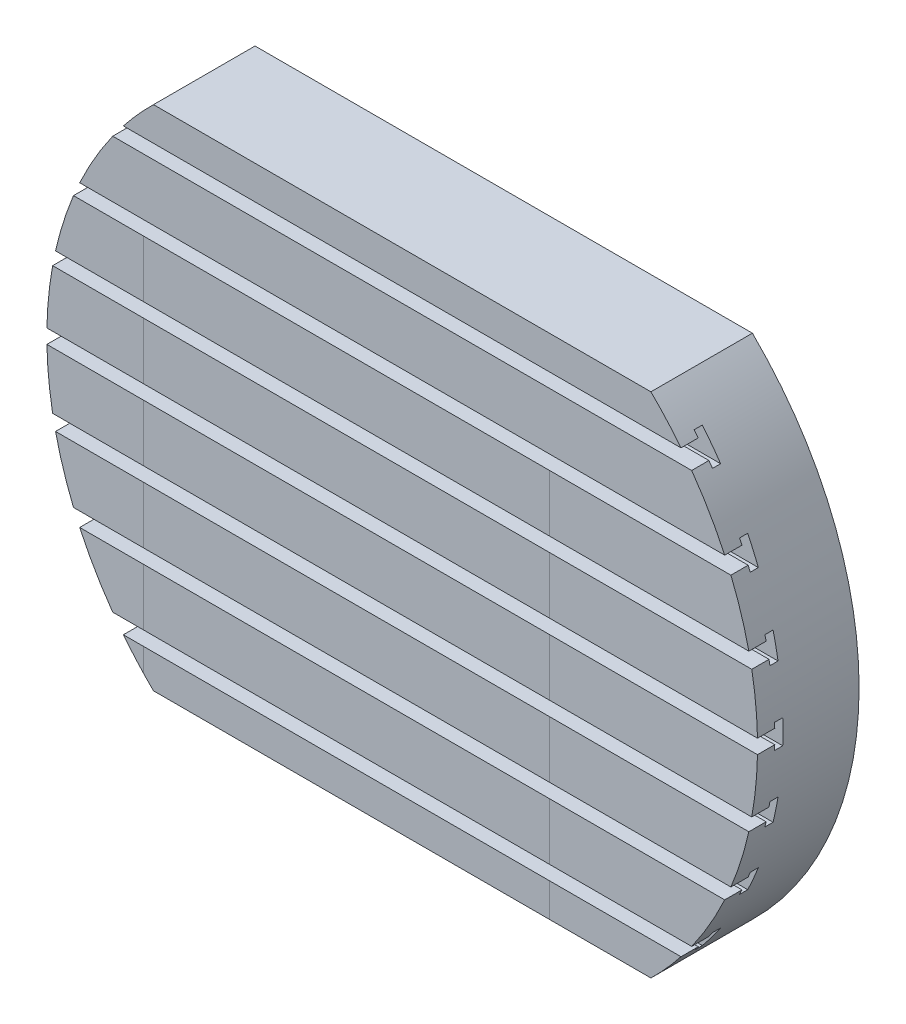
SolidWorks part; units mm, degrees
material "Plain Carbon Steel"
ref_plane "Front Plane" through (0, 0, 0) normal (0, 0, 1) x (1, 0, 0)
ref_plane "Top Plane" through (0, 0, 0) normal (0, 1, 0) x (1, 0, 0)
ref_plane "Right Plane" through (0, 0, 0) normal (1, 0, 0) x (0, 0, -1)
sketch "Sketch1" plane through (0, 0, 0) normal (0, 0, 1) x (1, 0, 0)
  circle A0 centre (0, 0) radius 350
  dimension "D1" = 700
extrude "Boss-Extrude1" add sketch "Sketch1" along normal blind 100
sketch "Sketch2" plane through (0, 0, 0) normal (1, 0, 0) x (0, 0, -1)
  line L0 (-100, 7) -> (-83, 7)
  line L1 (-100, 350) -> (-100, -350) construction
  line L2 (-83, 7) -> (-83, 12)
  line L3 (-83, 12) -> (-75, 12)
  line L4 (-75, 12) -> (-75, -12)
  line L5 (-75, -12) -> (-83, -12)
  line L6 (-83, -12) -> (-83, -7)
  line L7 (-83, -7) -> (-100, -7)
  line L8 (-100, -7) -> (-100, 7)
  line L9 (-100, 0) -> (-75, 0) construction
  line L10 (-83, 7) -> (-83, -7) construction
  line L11 (-100, -77) -> (-100, -63)
  line L12 (-100, -63) -> (-83, -63)
  line L13 (-83, -77) -> (-100, -77)
  line L14 (-83, -82) -> (-83, -77)
  line L15 (-75, -82) -> (-83, -82)
  line L16 (-75, -58) -> (-75, -82)
  line L17 (-83, -58) -> (-75, -58)
  line L18 (-83, -63) -> (-83, -58)
  line L19 (-100, -147) -> (-100, -133)
  line L20 (-100, -133) -> (-83, -133)
  line L21 (-83, -147) -> (-100, -147)
  line L22 (-83, -152) -> (-83, -147)
  line L23 (-75, -152) -> (-83, -152)
  line L24 (-75, -128) -> (-75, -152)
  line L25 (-83, -128) -> (-75, -128)
  line L26 (-83, -133) -> (-83, -128)
  line L27 (-100, -217) -> (-100, -203)
  line L28 (-100, -203) -> (-83, -203)
  line L29 (-83, -217) -> (-100, -217)
  line L30 (-83, -222) -> (-83, -217)
  line L31 (-75, -222) -> (-83, -222)
  line L32 (-75, -198) -> (-75, -222)
  line L33 (-83, -198) -> (-75, -198)
  line L34 (-83, -203) -> (-83, -198)
  line L43 (0, -350) -> (0, 350) construction
  line L44 (-100, -350) -> (0, -350)
  line L45 (-100, -350) -> (-100, -250)
  line L46 (-100, -250) -> (0, -250)
  line L47 (0, -350) -> (0, -250)
  line L48 (-100, 63) -> (-100, 77)
  line L49 (-100, 350) -> (0, 350)
  line L50 (-100, 350) -> (-100, 250)
  line L51 (-100, 250) -> (0, 250)
  line L52 (0, 350) -> (0, 250)
  line L53 (-83, 63) -> (-100, 63)
  line L54 (-83, 58) -> (-83, 63)
  line L55 (-75, 58) -> (-83, 58)
  line L56 (-75, 82) -> (-75, 58)
  line L57 (-83, 82) -> (-75, 82)
  line L58 (-83, 77) -> (-83, 82)
  line L59 (-100, 77) -> (-83, 77)
  line L60 (-100, 133) -> (-100, 147)
  line L61 (-83, 133) -> (-100, 133)
  line L62 (-83, 128) -> (-83, 133)
  line L63 (-75, 128) -> (-83, 128)
  line L64 (-75, 152) -> (-75, 128)
  line L65 (-83, 152) -> (-75, 152)
  line L66 (-83, 147) -> (-83, 152)
  line L67 (-100, 147) -> (-83, 147)
  line L68 (-100, 203) -> (-100, 217)
  line L69 (-83, 203) -> (-100, 203)
  line L70 (-83, 198) -> (-83, 203)
  line L71 (-75, 198) -> (-83, 198)
  line L72 (-75, 222) -> (-75, 198)
  line L73 (-83, 222) -> (-75, 222)
  line L74 (-83, 217) -> (-83, 222)
  line L75 (-100, 217) -> (-83, 217)
  dimension "D1" = 14
  dimension "D2" = 24
  dimension "D3" = 17
  dimension "D4" = 8
  dimension "D6" = 56
  dimension "D7" = 100
  dimension "D8" = 100
  dimension "D10" = 56
  dimension "D5" = 4
  dimension "D9" = 4
extrude "Cut-Extrude1" cut sketch "Sketch2" against normal mid plane 1000
sketch "Sketch3" plane through (0, 0, 100) normal (0, 0, 1) x (1, 0, 0)
  line L0 (-244.949, -250) -> (244.949, -250) construction
  line L1 (-254.949, -260) -> (145.051, -260)
  line L2 (-254.949, -260) -> (-254.949, 140)
  line L3 (-254.949, 140) -> (145.051, 140)
  line L4 (145.051, -260) -> (145.051, 140)
  dimension "D1" = 400
  dimension "D2" = 400
  dimension "D3" = 10
  dimension "D4" = 10
split line "Split Line1"
